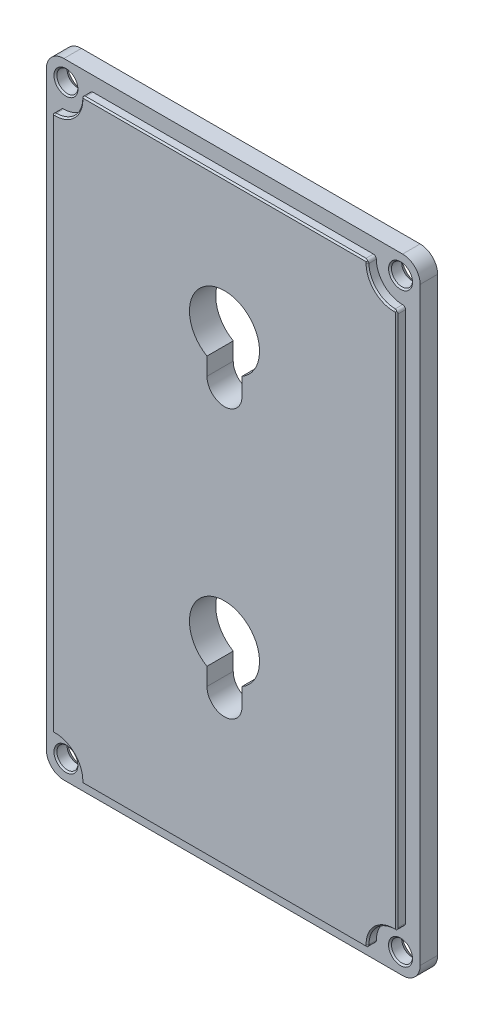
SolidWorks part; units mm, degrees
ref_plane "Front" through (0, 0, 0) normal (0, 0, 1) x (1, 0, 0)
ref_plane "Top" through (0, 0, 0) normal (0, 1, 0) x (1, 0, 0)
ref_plane "Right" through (0, 0, 0) normal (1, 0, 0) x (0, 0, -1)
sketch "Esquisse1" plane through (0, 0, 0) normal (0, 0, 1) x (1, 0, 0)
  line L4 (-33.0765, -242.5962) -> (-33.0765, -141.5962)
  line L5 (-94.0765, -245.5962) -> (-36.0765, -245.5962)
  line L6 (-97.0765, -141.5962) -> (-97.0765, -242.5962)
  line L7 (-36.0765, -138.5962) -> (-94.0765, -138.5962)
  line L8 (-33.0765, -242.5962) -> (-33.0765, -141.5962)
  line L9 (-94.0765, -245.5962) -> (-36.0765, -245.5962)
  line L10 (-97.0765, -141.5962) -> (-97.0765, -242.5962)
  line L11 (-36.0765, -138.5962) -> (-94.0765, -138.5962)
  arc A40 (-36.0765, -245.5962) -> (-33.0765, -242.5962) centre (-36.0765, -242.5962) ccw
  arc A41 (-36.0765, -245.5962) -> (-33.0765, -242.5962) centre (-36.0765, -242.5962) ccw
  arc A42 (-97.0765, -242.5962) -> (-94.0765, -245.5962) centre (-94.0765, -242.5962) ccw
  arc A43 (-97.0765, -242.5962) -> (-94.0765, -245.5962) centre (-94.0765, -242.5962) ccw
  arc A44 (-94.0765, -138.5962) -> (-97.0765, -141.5962) centre (-94.0765, -141.5962) ccw
  arc A45 (-94.0765, -138.5962) -> (-97.0765, -141.5962) centre (-94.0765, -141.5962) ccw
  arc A46 (-33.0765, -141.5962) -> (-36.0765, -138.5962) centre (-36.0765, -141.5962) ccw
  arc A47 (-33.0765, -141.5962) -> (-36.0765, -138.5962) centre (-36.0765, -141.5962) ccw
  dimension "D1" = 0
extrude "Boss.-Extru.1" add sketch "Esquisse1" along normal blind 3
sketch "Esquisse5" plane through (0, 0, 3) normal (0, 0, 1) x (1, 0, 0)
  line L116 (-40.5765, -243.0962) -> (-40.5765, -242.5962)
  line L117 (-36.0765, -238.0962) -> (-35.5765, -238.0962)
  line L118 (-35.5765, -238.0962) -> (-35.5765, -146.0962)
  line L119 (-35.5765, -146.0962) -> (-36.0765, -146.0962)
  line L120 (-40.5765, -141.5962) -> (-40.5765, -141.0962)
  line L121 (-40.5765, -141.0962) -> (-89.5765, -141.0962)
  line L122 (-89.5765, -141.0962) -> (-89.5765, -141.5962)
  line L123 (-94.0765, -146.0962) -> (-94.5765, -146.0962)
  line L124 (-94.5765, -146.0962) -> (-94.5765, -238.0962)
  line L125 (-94.5765, -238.0962) -> (-94.0765, -238.0962)
  line L126 (-89.5765, -242.5962) -> (-89.5765, -243.0962)
  line L127 (-89.5765, -243.0962) -> (-40.5765, -243.0962)
  line L128 (-40.5765, -243.0962) -> (-40.5765, -242.5962)
  line L129 (-36.0765, -238.0962) -> (-35.5765, -238.0962)
  line L130 (-35.5765, -238.0962) -> (-35.5765, -146.0962)
  line L131 (-35.5765, -146.0962) -> (-36.0765, -146.0962)
  line L132 (-40.5765, -141.5962) -> (-40.5765, -141.0962)
  line L133 (-40.5765, -141.0962) -> (-89.5765, -141.0962)
  line L134 (-89.5765, -141.0962) -> (-89.5765, -141.5962)
  line L135 (-94.0765, -146.0962) -> (-94.5765, -146.0962)
  line L136 (-94.5765, -146.0962) -> (-94.5765, -238.0962)
  line L137 (-94.5765, -238.0962) -> (-94.0765, -238.0962)
  line L138 (-89.5765, -242.5962) -> (-89.5765, -243.0962)
  line L139 (-89.5765, -243.0962) -> (-40.5765, -243.0962)
  arc A36 (-36.0765, -238.0962) -> (-40.5765, -242.5962) centre (-36.0765, -242.5962) ccw
  arc A37 (-40.5765, -141.5962) -> (-36.0765, -146.0962) centre (-36.0765, -141.5962) ccw
  arc A38 (-94.0765, -146.0962) -> (-89.5765, -141.5962) centre (-94.0765, -141.5962) ccw
  arc A39 (-89.5765, -242.5962) -> (-94.0765, -238.0962) centre (-94.0765, -242.5962) ccw
  arc A40 (-36.0765, -238.0962) -> (-40.5765, -242.5962) centre (-36.0765, -242.5962) ccw
  arc A41 (-40.5765, -141.5962) -> (-36.0765, -146.0962) centre (-36.0765, -141.5962) ccw
  arc A42 (-94.0765, -146.0962) -> (-89.5765, -141.5962) centre (-94.0765, -141.5962) ccw
  arc A43 (-89.5765, -242.5962) -> (-94.0765, -238.0962) centre (-94.0765, -242.5962) ccw
  dimension "D1" = 0.5
extrude "Boss.-Extru.2" add sketch "Esquisse5" along normal blind 1.5
sketch "Esquisse7" plane through (0, 0, 0) normal (0, 0, -1) x (-1, 0, 0)
  circle A0 centre (93.7229, -242.2427) radius 1.8
  circle A1 centre (93.7229, -141.9498) radius 1.8
  circle A2 centre (36.43, -141.9498) radius 1.8
  circle A3 centre (36.43, -242.2427) radius 1.8
  dimension "D1" = 3.6
extrude "Enlèv. mat.-Extru.1" cut sketch "Esquisse7" against normal up to next
chamfer "Chanfrein1" distance 1 angle 45 4 edges at (-95.5229, -242.2427, 0) (-38.23, -242.2427, 0) (-95.5229, -141.9498, 0) (-38.23, -141.9498, 0)
chamfer "Chanfrein2" distance 0.25 angle 45 20 edges at (-89.5765, -242.8462, 4.5) (-90.8945, -239.4143, 4.5) (-94.3265, -238.0962, 4.5) (-94.5765, -192.0962, 4.5) (-94.3265, -146.0962, 4.5) (-90.8945, -144.7782, 4.5) (-89.5765, -141.3462, 4.5) (-65.0765, -141.0962, 4.5) (-40.5765, -141.3462, 4.5) (-39.2584, -144.7782, 4.5) (-35.8265, -146.0962, 4.5) (-35.5765, -192.0962, 4.5) (-35.8265, -238.0962, 4.5) (-39.2584, -239.4143, 4.5) (-40.5765, -242.8462, 4.5) (-65.0765, -243.0962, 4.5) (-34.63, -242.2427, 3) (-91.9229, -242.2427, 3) (-91.9229, -141.9498, 3) (-34.63, -141.9498, 3)
fillet "Congé1" radius 0.5 8 edges at (-94.5765, -238.0962, 3.625) (-89.5765, -243.0962, 3.625) (-35.5765, -146.0962, 3.625) (-40.5765, -141.0962, 3.625) (-89.5765, -141.0962, 3.625) (-94.5765, -146.0962, 3.625) (-35.5765, -238.0962, 3.625) (-40.5765, -243.0962, 3.625)
sketch "Esquisse8" plane through (0, 0, 4.5) normal (0, 0, 1) x (1, 0, 0)
  line L0 (-65.0765, -141.0962) -> (-65.0765, -242.8462) construction
  line L1 (-41.0765, -141.0962) -> (-89.0765, -141.0962) construction
  line L2 (-89.3265, -242.8462) -> (-40.8265, -242.8462) construction
  line L3 (-65.0765, -191.9712) -> (12.0964, -191.9712) construction
  line L4 (-62.0765, -171.9712) -> (-68.0765, -171.9712) construction
  line L5 (-68.0765, -171.9712) -> (-68.0765, -168.9712)
  line L6 (-62.0765, -171.9712) -> (-62.0765, -168.9712)
  line L7 (-68.0765, -217.9712) -> (-68.0765, -214.9712)
  line L8 (-62.0765, -217.9712) -> (-62.0765, -214.9712)
  line L9 (-62.0765, -217.9712) -> (-68.0765, -217.9712) construction
  line L10 (-62.0765, -214.9712) -> (-62.0765, -168.9712) construction
  line L11 (-62.0765, -214.9712) -> (-65.0765, -191.9712) construction
  line L12 (-65.0765, -191.9712) -> (-62.0765, -168.9712) construction
  arc A0 (-68.0765, -171.9712) -> (-62.0765, -171.9712) centre (-65.0765, -171.9712) ccw
  arc A1 (-68.0765, -168.9712) -> (-62.0765, -168.9712) centre (-65.0765, -163.7751) cw
  arc A2 (-68.0765, -217.9712) -> (-62.0765, -217.9712) centre (-65.0765, -217.9712) ccw
  arc A3 (-68.0765, -214.9712) -> (-62.0765, -214.9712) centre (-65.0765, -209.7751) cw
  dimension "D1" = 20
  dimension "D2" = 6
  dimension "D3" = 3
  dimension "D4" = 6
  dimension "D5" = 2
extrude "Enlèv. mat.-Extru.2" cut sketch "Esquisse8" against normal through all
